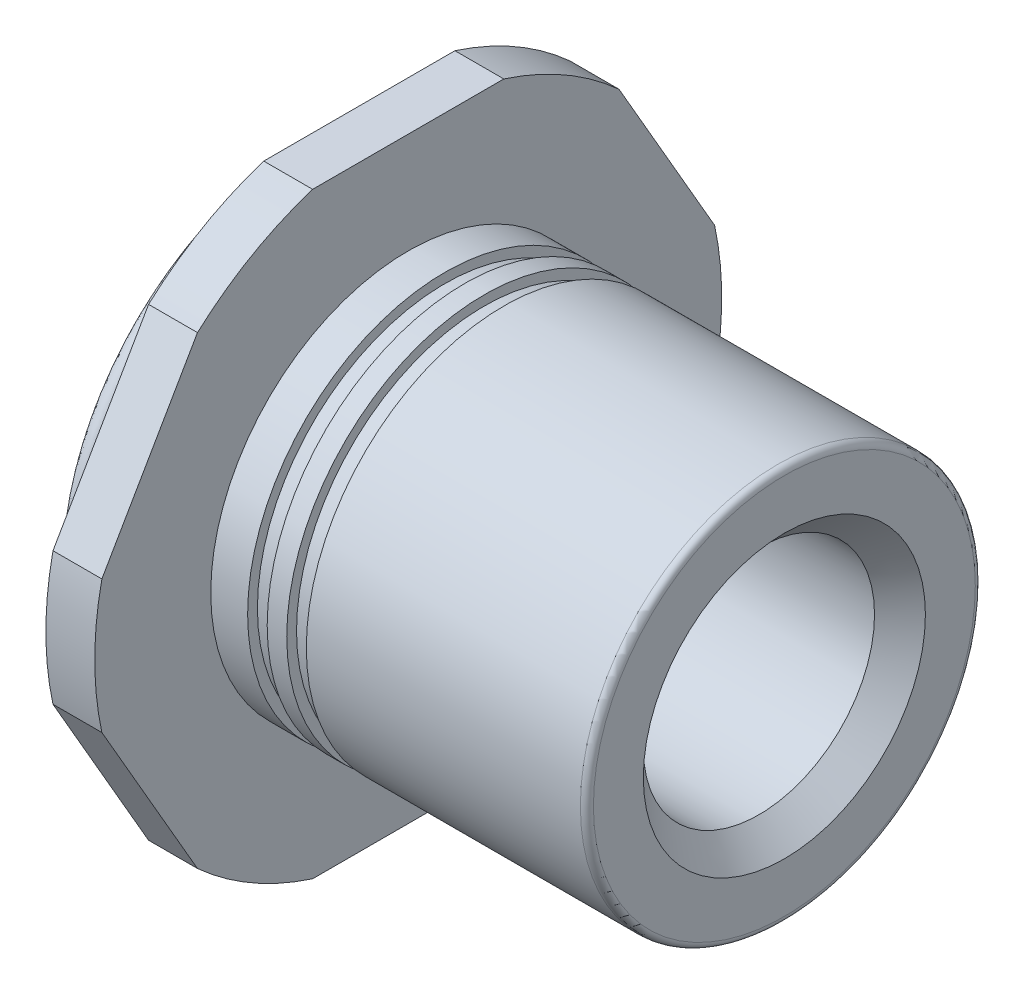
SolidWorks part; units mm, degrees
ref_plane "Front Plane" through (0, 0, 0) normal (0, 0, 1) x (1, 0, 0)
ref_plane "Top Plane" through (0, 0, 0) normal (0, 1, 0) x (1, 0, 0)
ref_plane "Right Plane" through (0, 0, 0) normal (1, 0, 0) x (0, 0, -1)
ref_plane "Plane4" through (-0.52, 0, 0) normal (-1, 0, 0) x (0, -1, 0)
sketch "Sketch1" plane through (-0.52, 0, 0) normal (-1, 0, 0) x (0, -1, 0)
  line L0 (-3.175, 1.0165) -> (-3.175, -1.0165)
  line L1 (-2.4678, -2.2414) -> (-0.7072, -3.2579)
  line L2 (0.7072, -3.2579) -> (2.4678, -2.2414)
  line L3 (3.175, -1.0165) -> (3.175, 1.0165)
  line L4 (2.4678, 2.2414) -> (0.7072, 3.2579)
  line L5 (-0.7072, 3.2579) -> (-2.4678, 2.2414)
  arc A0 (-3.175, -1.0165) -> (-2.4678, -2.2414) centre (0, 0) ccw
  arc A1 (-0.7072, -3.2579) -> (0.7072, -3.2579) centre (0, 0) ccw
  arc A2 (2.4678, -2.2414) -> (3.175, -1.0165) centre (0, 0) ccw
  arc A3 (3.175, 1.0165) -> (2.4678, 2.2414) centre (0, 0) ccw
  arc A4 (0.7072, 3.2579) -> (-0.7072, 3.2579) centre (0, 0) ccw
  arc A5 (-2.4678, 2.2414) -> (-3.175, 1.0165) centre (0, 0) ccw
extrude "Boss-Extrude1" add sketch "Sketch1" against normal blind 0.52
ref_plane "Plane5" through (0, 0, 0) normal (0, 0, -1) x (-1, 0, 0)
sketch "Sketch2" plane through (0, 0, 0) normal (0, 0, -1) x (-1, 0, 0)
  line L0 (0.52, 2.4954) -> (0.52, 0)
  line L1 (0.52, 0) -> (1.04, 0)
  line L2 (1.04, 0) -> (1.04, 2.591)
  line L3 (0.8625, 2.6645) -> (0.6933, 2.4954)
  line L4 (0.6933, 2.4954) -> (0.52, 2.4954)
  line L5 (0.52, 0) -> (1.0459, 0) construction
  spline S0 degree 3 poles (0.8625, 2.6645) (0.8707, 2.6728) (0.8805, 2.6797) (0.8909, 2.6847) (0.9014, 2.6898) (0.9129, 2.6931) (0.9245, 2.6944) (0.9361, 2.6956) (0.948, 2.695) (0.9594, 2.6923) (0.9707, 2.6897) (0.9818, 2.6851) (0.9916, 2.6789) (1.0014, 2.6727) (1.0103, 2.6647) (1.0176, 2.6555) (1.0248, 2.6464) (1.0305, 2.6359) (1.0343, 2.6249) (1.0381, 2.6141) (1.04, 2.6025) (1.04, 2.591) knots 0 0 0 0 0.000035 0.000035 0.000035 0.00007 0.00007 0.00007 0.000105 0.000105 0.000105 0.00014 0.00014 0.00014 0.000175 0.000175 0.000175 0.00021 0.00021 0.00021 0.000244 0.000244 0.000244 0.000244
revolve "Revolve1" add sketch "Sketch2" angle 360 about L5 reverse direction yes
sketch "Sketch3" plane through (0, 0, 0) normal (0, 0, -1) x (-1, 0, 0)
  line L0 (-4, 2.1) -> (-4, 0)
  line L1 (-4, 0) -> (0, 0)
  line L2 (0, 0) -> (0, 2.1)
  line L3 (0, 2.1) -> (-0.392, 2.1)
  line L4 (-0.392, 2.1) -> (-0.392, 1.996)
  line L5 (-0.392, 1.996) -> (-0.6, 1.996)
  line L6 (-0.6, 1.996) -> (-0.6, 2.1)
  line L7 (-0.6, 2.1) -> (-0.808, 2.1)
  line L8 (-0.808, 2.1) -> (-0.808, 1.996)
  line L9 (-0.808, 1.996) -> (-1.016, 1.996)
  line L10 (-1.016, 1.996) -> (-1.016, 2.1)
  line L11 (-1.016, 2.1) -> (-4, 2.1)
  line L12 (-4, 0) -> (0, 0) construction
revolve "Revolve2" add sketch "Sketch3" angle 360 about L12 reverse direction yes
hole_wizard "M2 Clearance Hole1" positions "Sketch5" profile "Sketch4" hole size "M2" standard "ANSI Metric"
sketch "Sketch5" plane through (-1.04, 0, 0) normal (-1, 0, 0) x (0, 0, 1)
  point P0 (0, 0)
sketch "Sketch4" plane through (-1.04, 0, 0) normal (0, 1, 0) x (0, 0, 1)
  line L0 (0, 0) -> (0, 5.04)
  line L1 (0, 5.04) -> (1.2295, 5.04)
  line L2 (1.2295, 5.04) -> (1.2295, 0)
  line L5 (1.2295, 0) -> (0, 0)
  line L11 (0, -6.35) -> (0, 107.95) construction
  dimension "Thru Hole Dia." = 2.459
  dimension "Thru Hole Depth" = 5.04
chamfer "Chamfer1" distance 0.2705 angle 45 2 edges at (4, 0, 1.2295) (-1.04, 0, 1.2295)
fillet "Fillet1" radius 0.0693 1 edges at (4, 0, 2.1) tangent propagation no
